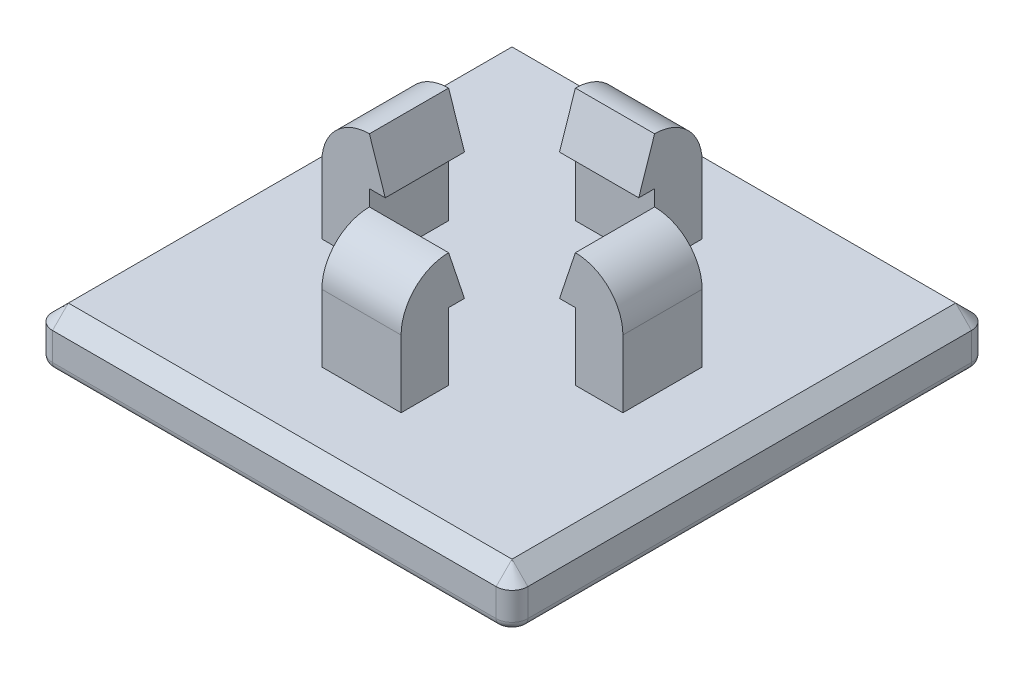
SolidWorks part; units mm, degrees
ref_plane "Front Plane" through (0, 0, 0) normal (0, 0, 1) x (1, 0, 0)
ref_plane "Top Plane" through (0, 0, 0) normal (0, 1, 0) x (1, 0, 0)
ref_plane "Right Plane" through (0, 0, 0) normal (1, 0, 0) x (0, 0, -1)
sketch "Sketch1" plane through (0, 0, 0) normal (0, 1, 0) x (1, 0, 0)
  line L0 (-7.62, 7.112) -> (-7.62, -7.112)
  line L1 (-7.112, -7.62) -> (7.112, -7.62)
  line L2 (7.62, -7.112) -> (7.62, 7.112)
  line L3 (7.112, 7.62) -> (-7.112, 7.62)
  line L4 (-1.27, 4.826) -> (1.27, 4.826)
  line L5 (1.27, 4.826) -> (1.27, 3.302)
  line L6 (1.27, 3.302) -> (-1.27, 3.302)
  line L7 (-1.27, 3.302) -> (-1.27, 4.826)
  line L8 (3.302, 1.27) -> (4.826, 1.27)
  line L9 (4.826, 1.27) -> (4.826, -1.27)
  line L10 (4.826, -1.27) -> (3.302, -1.27)
  line L11 (3.302, -1.27) -> (3.302, 1.27)
  line L12 (1.27, -3.302) -> (1.27, -4.826)
  line L13 (1.27, -4.826) -> (-1.27, -4.826)
  line L14 (-1.27, -4.826) -> (-1.27, -3.302)
  line L15 (-1.27, -3.302) -> (1.27, -3.302)
  line L16 (-3.302, -1.27) -> (-4.826, -1.27)
  line L17 (-4.826, -1.27) -> (-4.826, 1.27)
  line L18 (-4.826, 1.27) -> (-3.302, 1.27)
  line L19 (-3.302, 1.27) -> (-3.302, -1.27)
  arc A0 (-7.62, -7.112) -> (-7.112, -7.62) centre (-7.112, -7.112) ccw
  arc A1 (7.112, -7.62) -> (7.62, -7.112) centre (7.112, -7.112) ccw
  arc A2 (7.62, 7.112) -> (7.112, 7.62) centre (7.112, 7.112) ccw
  arc A3 (-7.112, 7.62) -> (-7.62, 7.112) centre (-7.112, 7.112) ccw
  circle A4 centre (0, 0) radius 4.064
  point P37 (0, 0)
  dimension "D1" = 0.508
  dimension "D3" = 8.128
  dimension "D2" = 4
  dimension "D4" = 4.826
  dimension "D5" = 1.524
  dimension "D6" = 2.54
extrude "Boss-Extrude1" add sketch "Sketch1" along normal blind 1.651 contours L3 A3 L0 A0 L1 A1 L2 A2 A4 L12 L13 L14 L16 L17 L18 L7 L4 L5 L8 L9 L10 | L12 A4 L10 L11 L8 L5 L6 L7 L18 L19 L16 L14 L15 region at (-7.3188, 0, -7.3188) region at (0, 0, 0)
extrude "Boss-Extrude2" add sketch "Sketch1<3>" along normal blind 5.334 contours A4 L18 L17 L16 | L18 A4 L16 L19 | L14 A4 L12 L15 | A4 L14 L13 L12 | L5 A4 L7 L6 | A4 L5 L4 L7 | A4 L10 L9 L8 | L10 A4 L8 L11 region at (0, 0, -4.4092) region at (0, 0, -3.6521) region at (-4.4092, 0, 0) region at (-3.6521, 0, 0) region at (3.6521, 0, 0) region at (4.4092, 0, 0) region at (0, 0, 4.4092) region at (0, 0, 3.6521)
sketch "Sketch1<3>" plane through (0, 0, 0) normal (0, 1, 0) x (1, 0, 0) same geometry as "Sketch1"
fillet "Fillet1" radius 1.524 4 edges at (-4.826, 5.334, 0) (0, 5.334, -4.826) (4.826, 5.334, 0) (0, 5.334, 4.826)
chamfer "Chamfer1" distance 0.508 angle 45 8 edges at (7.62, 1.651, 0) (0, 1.651, -7.62) (-7.62, 1.651, 0) (-7.4712, 1.651, -7.4712) (7.4712, 1.651, -7.4712) (-7.4712, 1.651, 7.4712) (7.4712, 1.651, 7.4712) (0, 1.651, 7.62)
fillet "Fillet2" radius 0.254 8 edges at (7.4712, 0, -7.4712) (7.4712, 0, 7.4712) (-7.4712, 0, 7.4712) (-7.4712, 0, -7.4712) (0, 0, 7.62) (7.62, 0, 0) (0, 0, -7.62) (-7.62, 0, 0)
sketch "Sketch2" plane through (0, 0, -1.27) normal (0, 0, -1) x (-1, 0, 0)
  line L0 (-3.302, 5.334) -> (-2.794, 3.81)
  line L1 (-2.794, 3.81) -> (-3.302, 3.81)
  line L2 (-3.302, 3.81) -> (-3.302, 5.334)
  line L3 (0, 5.334) -> (0, 1.651) construction
  line L4 (-1.27, 5.334) -> (1.27, 5.334) construction
  line L5 (1.27, 1.651) -> (-1.27, 1.651) construction
  line L6 (2.794, 3.81) -> (3.302, 3.81)
  line L7 (3.302, 5.334) -> (2.794, 3.81)
  line L8 (3.302, 3.81) -> (3.302, 5.334)
  point P14 (-2.7971, 3.81)
  dimension "D1" = 0.508
extrude "Boss-Extrude3" add sketch "Sketch2" against normal blind 2.54
sketch "Sketch3" plane through (-1.27, 0, 0) normal (-1, 0, 0) x (0, 0, 1)
  line L0 (-3.302, 5.334) -> (-2.794, 3.81)
  line L1 (-2.794, 3.81) -> (-3.302, 3.81)
  line L2 (-3.302, 3.81) -> (-3.302, 5.334)
  line L3 (0, 5.334) -> (0, 1.651)
  line L4 (-1.27, 5.334) -> (1.27, 5.334) construction
  line L5 (1.27, 1.651) -> (-1.27, 1.651) construction
  line L6 (2.794, 3.81) -> (3.302, 3.81)
  line L7 (3.302, 5.334) -> (2.794, 3.81)
  line L8 (3.302, 3.81) -> (3.302, 5.334)
  line M5 (-3.302, 1.651) -> (-3.302, 5.334)
  dimension "D1" = 0.508
extrude "Boss-Extrude4" add sketch "Sketch3" against normal blind 2.54 contours L1 L0 M5 | L6 L8 L7 region at (-1.27, 4.318, -3.1327) region at (-1.27, 4.318, 3.1327)
